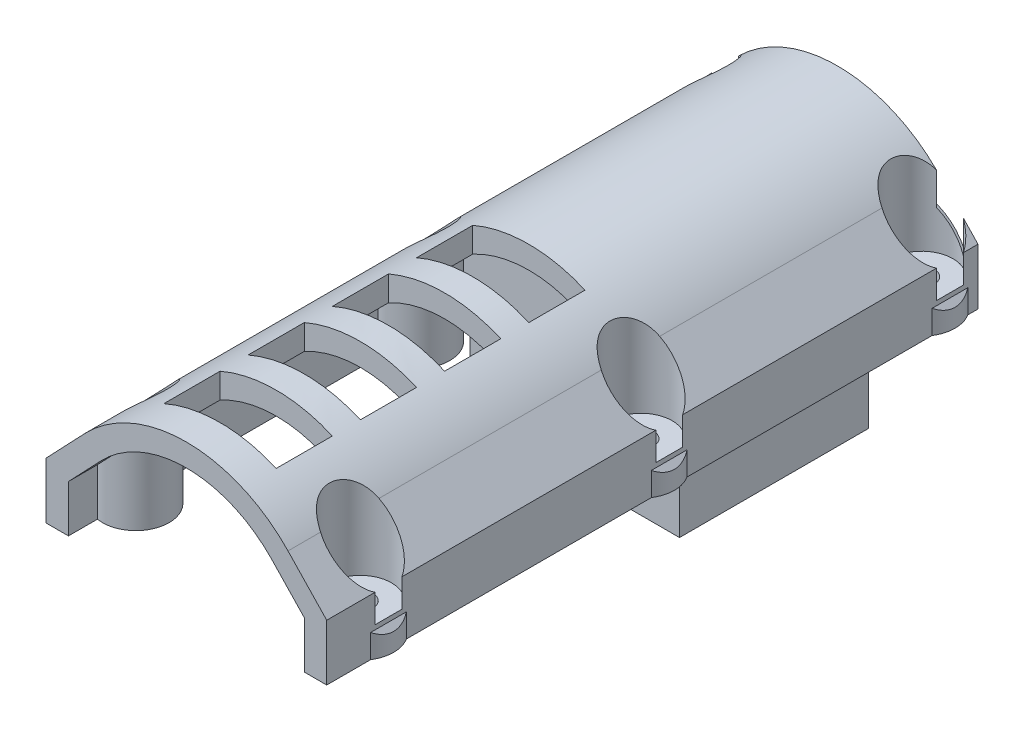
SolidWorks part; units mm, degrees
material "ABS"
ref_plane "Ön Düzlem" through (0, 0, 0) normal (0, 0, 1) x (1, 0, 0)
ref_plane "Üst Düzlem" through (0, 0, 0) normal (0, 1, 0) x (1, 0, 0)
ref_plane "Sağ Düzlem" through (0, 0, 0) normal (1, 0, 0) x (0, 0, -1)
sketch "Sketch1" plane through (0, 0, 0) normal (0, 0, 1) x (1, 0, 0)
  line L1 (-25, 0) -> (-25, 10)
  line L3 (25, 10) -> (25, 0)
  line L5 (-25, 10) -> (-18.1034, 17.2414)
  line L6 (18.1034, 17.2414) -> (25, 10)
  line L12 (-38.4691, 0) -> (30.8694, 0) construction
  line L13 (0, -28.1952) -> (0, -25) construction
  line L14 (0, 0) -> (-18.1034, 17.2414) construction
  line L15 (0, 0) -> (18.1034, 17.2414) construction
  line L16 (0, 0) -> (0, 28.1638) construction
  line L17 (-25, 0) -> (25, 0)
  arc A2 (18.1034, 17.2414) -> (-18.1034, 17.2414) centre (0, 0) ccw
  point P4 (0, 0)
  dimension "D2" = 10
  dimension "D3" = 25
  dimension "D4" = 43.603
  dimension "D5" = 43.603
  dimension "D6" = 17.2414
extrude "Boss-Extrude1" add sketch "Sketch1" along normal blind 116
shell "Shell1" thickness 4 removed face at (0, 0, 58) removed face at (0, 10.3736, 116)
sketch "Sketch4" plane through (0, 0, 0) normal (0, -1, 0) x (1, 0, 0)
  line L0 (-25, 116) -> (-25, 0) construction
  line L3 (0, 5) -> (0, 55) construction
  line L4 (0, 55) -> (0, 105) construction
  line L8 (-25, 0) -> (25, 0) construction
  circle A0 centre (-20, 5) radius 5.925
  circle A1 centre (-20, 55) radius 5.925
  circle A2 centre (-20, 105) radius 5.925
  circle A3 centre (20, 105) radius 5.925
  circle A4 centre (20, 55) radius 5.925
  circle A5 centre (20, 5) radius 5.925
  dimension "D1" = 11.85
  dimension "D2" = 5
  dimension "D3" = 50
  dimension "D4" = 50
  dimension "D5" = 5
  dimension "D6" = 5
  dimension "D7" = 5
extrude "Boss-Extrude2" add sketch "Sketch4" against normal up to surface (15.6712 mm away) contours A0 | A1 | A2 up to face at (-18.1034, 11.4414, 60)
extrude "Boss-Extrude3" add sketch "Sketch4<3>" against normal up to surface (15.6712 mm away) contours A3 | A4 | A5 up to face at (18.1034, 11.4414, 60)
sketch "Sketch4<3>" plane through (0, 0, 0) normal (0, -1, 0) x (1, 0, 0) same geometry as "Sketch4"
sketch "Sketch5" plane through (0, 0, 0) normal (0, -1, 0) x (1, 0, 0)
  line L0 (0, -7.0614) -> (0, 128.9064) construction
  circle A0 centre (-20, 5) radius 2.25
  circle A1 centre (-20, 55) radius 2.25
  circle A2 centre (-20, 105) radius 2.25
  circle A3 centre (20, 105) radius 2.25
  circle A4 centre (20, 55) radius 2.25
  circle A5 centre (20, 5) radius 2.25
  dimension "D1" = 4.5
extrude "Cut-Extrude1" cut sketch "Sketch5" against normal up to next
ref_plane "Plane2" through (0, 25, 0) normal (0, 1, 0) x (1, 0, 0)
sketch "Sketch6" plane through (0, 25, 0) normal (0, 1, 0) x (1, 0, 0)
  line L2 (0, -121.9546) -> (0, 6.4416) construction
  circle A0 centre (20, -105) radius 5.54
  circle A1 centre (20, -55) radius 5.54
  circle A2 centre (20, -5) radius 5.54
  circle A3 centre (-20, -5) radius 5.54
  circle A4 centre (-20, -55) radius 5.54
  circle A5 centre (-20, -105) radius 5.54
  dimension "D3" = 11.08
extrude "Cut-Extrude2" cut sketch "Sketch6" against normal offset from surface (20 mm away) 5 up to face at (17.75, 0, 5)
sketch "Sketch7" plane through (0, 25, 0) normal (0, 1, 0) x (1, 0, 0)
  line L1 (-18.1034, -116) -> (18.1034, -116) construction
  line L3 (10, -110) -> (-10, -110)
  line L4 (10, -110) -> (10, -100)
  line L5 (10, -100) -> (-10, -100)
  line L6 (-10, -110) -> (-10, -100)
  line L7 (10, -110) -> (-10, -100) construction
  line L8 (10, -100) -> (-10, -110) construction
  line L11 (10, -95) -> (10, -85)
  line L12 (10, -95) -> (-10, -95)
  line L13 (-10, -95) -> (-10, -85)
  line L14 (10, -85) -> (-10, -85)
  line L15 (10, -80) -> (10, -70)
  line L16 (10, -80) -> (-10, -80)
  line L17 (-10, -80) -> (-10, -70)
  line L18 (10, -70) -> (-10, -70)
  line L19 (10, -65) -> (10, -55)
  line L20 (10, -65) -> (-10, -65)
  line L21 (-10, -65) -> (-10, -55)
  line L22 (10, -55) -> (-10, -55)
  line L35 (10, -20) -> (10, -10) [skipped]
  line L36 (10, -20) -> (-10, -20) [skipped]
  line L37 (-10, -20) -> (-10, -10) [skipped]
  line L38 (10, -10) -> (-10, -10) [skipped]
  line L39 (10, -35) -> (10, -25) [skipped]
  line L40 (10, -35) -> (-10, -35) [skipped]
  line L41 (-10, -35) -> (-10, -25) [skipped]
  line L42 (10, -25) -> (-10, -25) [skipped]
  line L43 (10, -50) -> (10, -40) [skipped]
  line L44 (10, -50) -> (-10, -50) [skipped]
  line L45 (-10, -50) -> (-10, -40) [skipped]
  line L46 (10, -40) -> (-10, -40) [skipped]
  point P5 (0, -105)
  dimension "D1" = 10
  dimension "D2" = 20
  dimension "D3" = 6
  dimension "D4" = 7
extrude "Cut-Extrude3" cut sketch "Sketch7" against normal up to next
sketch "Sketch8" plane through (0, 0, 0) normal (0, -1, 0) x (1, 0, 0)
  line L1 (21, 10.84) -> (21, 46.84)
  line L2 (21, 49.16) -> (21, 10.84) construction
  line L3 (21, 46.84) -> (-21, 46.84)
  line L4 (-21, 49.16) -> (-21, 10.84) construction
  line L5 (-21, 46.84) -> (-21, 10.84)
  line L7 (-14.16, 4) -> (14.16, 4)
  arc A0 (21, 10.84) -> (14.16, 4) centre (20, 5) ccw construction
  arc A1 (-14.16, 4) -> (-21, 10.84) centre (-20, 5) ccw construction
  arc A2 (-14.16, 4) -> (-21, 10.84) centre (-20, 5) ccw
  arc A3 (21, 10.84) -> (14.16, 4) centre (20, 5) ccw
extrude "Boss-Extrude14" add sketch "Sketch8" against normal blind 13
sketch "Sketch10" plane through (0, 0, 0) normal (0, -1, 0) x (1, 0, 0)
  line L0 (18.67, 46.835) -> (18.67, 13.1512)
  line L2 (-11.8654, 6.4281) -> (11.8654, 6.4281)
  line L14 (18.67, 46.835) -> (-18.67, 46.835)
  line L16 (-18.67, 46.835) -> (-18.67, 13.1512)
  arc A0 (18.67, 13.1512) -> (11.8654, 6.4281) centre (20, 5) ccw
  arc A1 (-11.8654, 6.4281) -> (-18.67, 13.1512) centre (-20, 5) ccw
extrude "Boss-Extrude15" add sketch "Sketch10" along normal blind 15
sketch "Sketch11" plane through (0, -15, 0) normal (0, -1, 0) x (1, 0, 0)
  line L0 (5, 6.4281) -> (-7, 6.4281)
  line L2 (-11.8654, 6.4281) -> (11.8654, 6.4281) construction
  line L3 (5, 6.4281) -> (5, 38.4281)
  line L4 (5, 38.4281) -> (-7, 38.4281)
  line L5 (-7, 38.4281) -> (-7, 6.4281)
  line L6 (18.67, 13.1512) -> (18.67, 46.835) construction
  dimension "D1" = 32
  dimension "D2" = 13.67
  dimension "D3" = 12
extrude "Cut-Extrude5" cut sketch "Sketch11" against normal blind 1
sketch "Sketch12" plane through (0, -14, 0) normal (0, -1, 0) x (1, 0, 0)
  line L1 (-7, 38.4281) -> (-7, 6.4281) construction
  line L2 (-7, 11.4281) -> (-7, 33.4281)
  line L3 (-7, 33.4281) -> (5, 33.4281)
  line L4 (5, 6.4281) -> (5, 38.4281) construction
  line L5 (5, 33.4281) -> (5, 11.4281)
  line L6 (5, 11.4281) -> (-7, 11.4281)
extrude "Cut-Extrude6" cut sketch "Sketch12" against normal blind 18
sketch "Sketch13" plane through (0, -14, 0) normal (0, -1, 0) x (1, 0, 0)
  line L0 (5, 33.4281) -> (-7, 33.4281) construction
  line L2 (5, 6.4281) -> (5, 38.4281) construction
  line L4 (-7, 11.4281) -> (5, 11.4281) construction
  circle A0 centre (-1, 8.5281) radius 1
  circle A1 centre (-1, 36.3281) radius 1
  dimension "D1" = 2
  dimension "D2" = 2
  dimension "D4" = 6
  dimension "D5" = 6
  dimension "D6" = 2.9
  dimension "D3" = 2.9
extrude "Cut-Extrude7" cut sketch "Sketch13" against normal blind 15
sketch "Sketch14" plane through (0, 0, 0) normal (0, -1, 0) x (1, 0, 0)
  line L0 (-23, -2.2511) -> (-23, 29.3438) construction
  line L1 (-26.563, 10) -> (-20.1587, 10) construction
  line L2 (-27.1029, 25) -> (-20.1587, 25) construction
  line L3 (-25, 1.8211) -> (-25, 0) construction
  line L4 (-25, 0) -> (-23.1789, 0) construction
  line L5 (-25, 51.8211) -> (-25, 8.1789) construction
  line L6 (0, 0) -> (0, -12.7194) construction
  line L7 (27.1029, 25) -> (20.1587, 25) construction
  line L8 (26.563, 10) -> (20.1587, 10) construction
  line L9 (23, -2.2511) -> (23, 29.3438) construction
  circle A0 centre (-23, 10) radius 0.5
  circle A1 centre (-23, 25) radius 0.5
  circle A2 centre (23, 25) radius 0.5
  circle A3 centre (23, 10) radius 0.5
  dimension "D1" = 2
  dimension "D3" = 1
  dimension "D5" = 1
  dimension "D6" = 2
  dimension "D2" = 10
  dimension "D4" = 15
extrude "Cut-Extrude8" cut sketch "Sketch14" against normal blind 10
